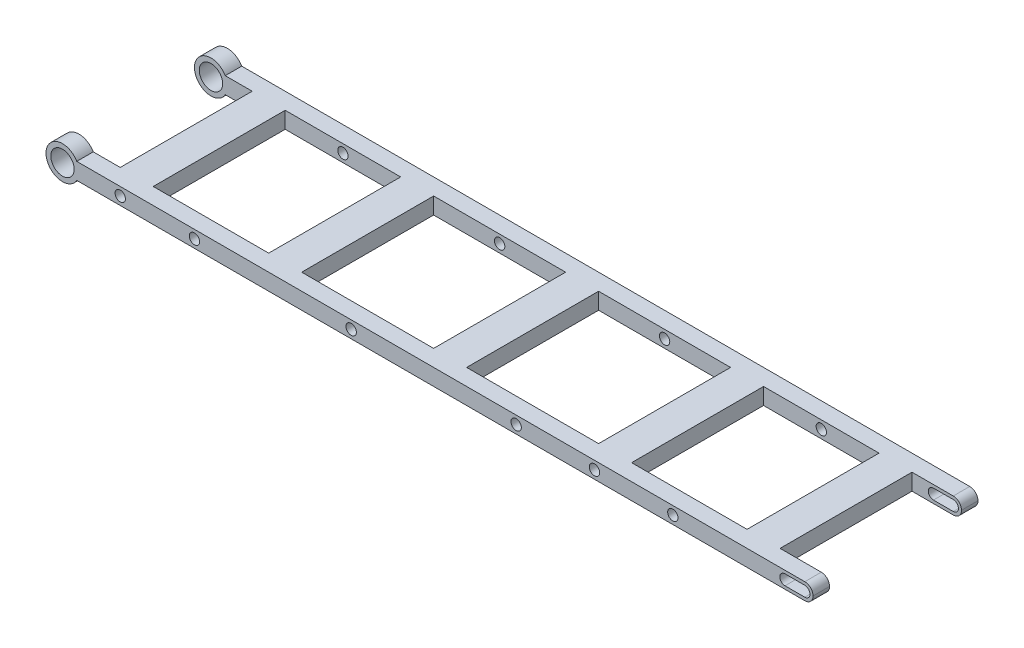
SolidWorks part; units mm, degrees
ref_plane "Front Plane" through (0, 0, 0) normal (0, 0, 1) x (1, 0, 0)
ref_plane "Top Plane" through (0, 0, 0) normal (0, 1, 0) x (1, 0, 0)
ref_plane "Right Plane" through (0, 0, 0) normal (1, 0, 0) x (0, 0, -1)
sketch "Sketch1" plane through (0, 0, 0) normal (0, 1, 0) x (1, 0, 0)
  line L0 (-146.05, 25.4) -> (-127, 25.4)
  line L1 (-146.05, 31.75) -> (146.05, 31.75)
  line L2 (-146.05, 31.75) -> (-146.05, 25.4)
  line L3 (-146.05, -31.75) -> (146.05, -31.75)
  line L4 (146.05, 31.75) -> (146.05, 25.4)
  line L5 (-146.05, 31.75) -> (146.05, -31.75) construction
  line L6 (-146.05, -31.75) -> (146.05, 31.75) construction
  line L8 (-146.05, -25.4) -> (-127, -25.4)
  line L10 (0, 31.75) -> (0, -31.75) construction
  line L11 (-6.35, 25.4) -> (-6.35, -25.4)
  line L12 (127, 25.4) -> (127, -25.4)
  line L14 (-6.35, 31.75) -> (-6.35, -31.75) construction
  line L15 (-57.15, 25.4) -> (-57.15, -25.4)
  line L20 (-69.85, 25.4) -> (-69.85, -25.4)
  line L21 (-114.3, 25.4) -> (-114.3, -25.4)
  line L22 (-127, 25.4) -> (-127, -25.4)
  line L23 (-146.05, -25.4) -> (-146.05, -31.75)
  line L24 (146.05, -25.4) -> (146.05, -31.75)
  line L32 (-114.3, 25.4) -> (-69.85, 25.4)
  line L33 (-114.3, -25.4) -> (-69.85, -25.4)
  line L36 (-57.15, -25.4) -> (-6.35, -25.4)
  line L38 (-57.15, 25.4) -> (-6.35, 25.4)
  line L47 (127, -25.4) -> (146.05, -25.4)
  line L48 (127, 25.4) -> (146.05, 25.4)
  line L50 (57.15, 25.4) -> (6.35, 25.4)
  line L51 (6.35, 25.4) -> (6.35, -25.4)
  line L52 (57.15, -25.4) -> (6.35, -25.4)
  line L53 (57.15, 25.4) -> (57.15, -25.4)
  line L54 (114.3, 25.4) -> (69.85, 25.4)
  line L55 (69.85, 25.4) -> (69.85, -25.4)
  line L56 (114.3, -25.4) -> (69.85, -25.4)
  line L57 (114.3, 25.4) -> (114.3, -25.4)
  point P0 (0, 0)
  dimension "D1" = 63.5
  dimension "D2" = 292.1
  dimension "D4" = 6.35
  dimension "D3" = 6.35
  dimension "D14" = 6.35
  dimension "D5" = 19.05
  dimension "D7" = 44.45
  dimension "D8" = 19.05
  dimension "D6" = 50.8
  dimension "D13" = 12.7
extrude "Boss-Extrude1" add sketch "Sketch1" against normal blind 6.35
fillet "Fillet2" radius 3.175 8 edges at (-146.05, -6.35, 28.575) (-146.05, 0, 28.575) (-146.05, -6.35, -28.575) (-146.05, 0, -28.575) (146.05, -6.35, -28.575) (146.05, 0, -28.575) (146.05, -6.35, 28.575) (146.05, 0, 28.575)
sketch "Sketch2" plane through (0, 0, 31.75) normal (0, 0, 1) x (1, 0, 0)
  line L0 (-142.875, 0) -> (-142.875, -6.35) construction
  line L1 (0, 0) -> (0, -6.35) construction
  line L2 (-114.3, 0) -> (-69.85, 0) construction
  line L3 (-114.3, 0) -> (-69.85, 0)
  line L4 (142.875, 0) -> (-142.875, 0)
  line L5 (-57.15, 0) -> (-6.35, 0) construction
  line L6 (-142.875, -6.35) -> (142.875, -6.35)
  line L7 (-57.15, 0) -> (-6.35, 0)
  line L8 (142.875, 0) -> (-142.875, 0)
  line L10 (-142.875, -6.35) -> (142.875, -6.35)
  line L16 (-31.75, 0) -> (-31.75, -6.35) construction
  line L17 (-92.075, 0) -> (-92.075, -6.35) construction
  line L19 (135.255, -1.1811) -> (142.875, -1.1811)
  line L20 (31.75, 0) -> (31.75, -6.35) construction
  line L21 (135.255, -5.1689) -> (142.875, -5.1689)
  line L22 (92.075, 0) -> (92.075, -6.35) construction
  line L23 (-127, 0) -> (-142.875, 0) construction
  line L24 (-127, 0) -> (-142.875, 0)
  line L25 (-127, 0) -> (-114.3, 0)
  line L26 (31.75, -3.175) -> (92.075, -3.175)
  circle A0 centre (-142.875, -3.175) radius 6.35
  circle A5 centre (-142.875, -3.175) radius 4.4996
  circle A6 centre (-92.075, -3.175) radius 1.9939
  circle A15 centre (-31.75, -3.175) radius 1.9939
  circle A16 centre (31.75, -3.175) radius 1.9939
  circle A17 centre (92.075, -3.175) radius 1.9939
  arc A19 (-142.875, 0) -> (-146.05, -3.175) centre (-142.875, -3.175) ccw
  arc A20 (-142.875, 0) -> (-146.05, -3.175) centre (-142.875, -3.175) ccw
  arc A21 (-146.05, -3.175) -> (-142.875, -6.35) centre (-142.875, -3.175) ccw
  arc A22 (-146.05, -3.175) -> (-142.875, -6.35) centre (-142.875, -3.175) ccw
  arc A23 (142.875, -6.35) -> (146.05, -3.175) centre (142.875, -3.175) ccw
  arc A24 (142.875, -6.35) -> (146.05, -3.175) centre (142.875, -3.175) ccw
  arc A25 (146.05, -3.175) -> (142.875, 0) centre (142.875, -3.175) ccw
  arc A26 (146.05, -3.175) -> (142.875, 0) centre (142.875, -3.175) ccw
  arc A27 (142.875, -5.1689) -> (142.875, -1.1811) centre (142.875, -3.175) ccw
  arc A28 (135.255, -1.1811) -> (135.255, -5.1689) centre (135.255, -3.175) ccw
  circle A29 centre (-120.65, -3.175) radius 1.9939
  circle A30 centre (61.9125, -3.175) radius 1.9939
  point P15 (-92.075, 0)
  point P46 (61.9125, -3.175)
  dimension "D1" = 12.7
  dimension "D4" = 3.9878
  dimension "D5" = 3.9878
  dimension "D6" = 31.75
  dimension "D7" = 92.075
  dimension "D11" = 8.9992
  dimension "D12" = 3.9878
  dimension "D13" = 3.9878
  dimension "D14" = 22.225
  dimension "D15" = 3.9878
  dimension "D3" = 3.9878
  dimension "D8" = 3.9878
  dimension "D10" = 7.62
  dimension "D9" = 3.9878
  dimension "D2" = 0
extrude "Boss-Extrude3" add sketch "Sketch2" along direction (0, 0, -1) on the side against the normal up to surface (6.35 mm away) contours A0 up to face at (-137.423, -3.175, 25.4)
sketch "Sketch4" plane through (0, 0, -31.75) normal (0, 0, -1) x (-1, 0, 0)
  circle A0 centre (142.875, -3.175) radius 6.35 construction
  circle A1 centre (142.875, -3.175) radius 6.35
extrude "Boss-Extrude4" add sketch "Sketch4" against normal up to surface (6.35 mm away) up to face at (-137.423, -3.175, -25.4)
extrude "Cut-Extrude1" cut sketch "Sketch2<4>" against normal up to surface (63.5 mm away) contours L19 A28 L21 A27 | A5 | A6 | A15 | A16 | A17 | A29 | A30 region at (139.065, -3.175, 31.75) up to face at (29.3029, -3.175, -31.75)
sketch "Sketch2<4>" plane through (0, 0, 31.75) normal (0, 0, 1) x (1, 0, 0) same geometry as "Sketch2"
sketch "Sketch5" plane through (127, 0, 0) normal (1, 0, 0) x (0, 0, -1)
  line L6 (25.4, -3.175) -> (25.4, -6.35) construction
  line L7 (25.4, -6.35) -> (31.75, -6.35) construction
  line L8 (31.75, -6.35) -> (31.75, -3.175) construction
  line L9 (31.75, 0) -> (25.4, 0) construction
  line L10 (25.4, 0) -> (25.4, -3.175) construction
  line L11 (31.75, -3.175) -> (31.75, 0) construction
  line L12 (-31.75, -3.175) -> (-31.75, -6.35) construction
  line L13 (-31.75, -6.35) -> (-25.4, -6.35) construction
  line L14 (-25.4, -6.35) -> (-25.4, -3.175) construction
  line L15 (-25.4, 0) -> (-31.75, 0) construction
  line L16 (-31.75, 0) -> (-31.75, -3.175) construction
  line L17 (-25.4, -3.175) -> (-25.4, 0) construction
  line L18 (25.4, -3.175) -> (25.4, -6.35) construction
  line L19 (25.4, -6.35) -> (31.75, -6.35)
  line L20 (31.75, -6.35) -> (31.75, -3.175) construction
  line L21 (31.75, 0) -> (25.4, 0) construction
  line L22 (25.4, 0) -> (25.4, -3.175) construction
  line L23 (31.75, -3.175) -> (31.75, 0) construction
  line L24 (-31.75, -3.175) -> (-31.75, -6.35) construction
  line L25 (-31.75, -6.35) -> (-25.4, -6.35)
  line L26 (-25.4, -6.35) -> (-25.4, -3.175) construction
  line L27 (-25.4, 0) -> (-31.75, 0) construction
  line L28 (-31.75, 0) -> (-31.75, -3.175) construction
  line L29 (-25.4, -3.175) -> (-25.4, 0) construction
  line L30 (-31.75, -6.35) -> (-28.575, -9.525)
  line L31 (-28.575, -9.525) -> (-25.4, -6.35)
  line L32 (25.4, -6.35) -> (28.575, -9.525)
  line L33 (28.575, -9.525) -> (31.75, -6.35)
  dimension "D1" = 45
  dimension "D2" = 45
  dimension "D3" = 45
  dimension "D4" = 45
extrude "Boss-Extrude5" add sketch "Sketch5" against normal blind 127
